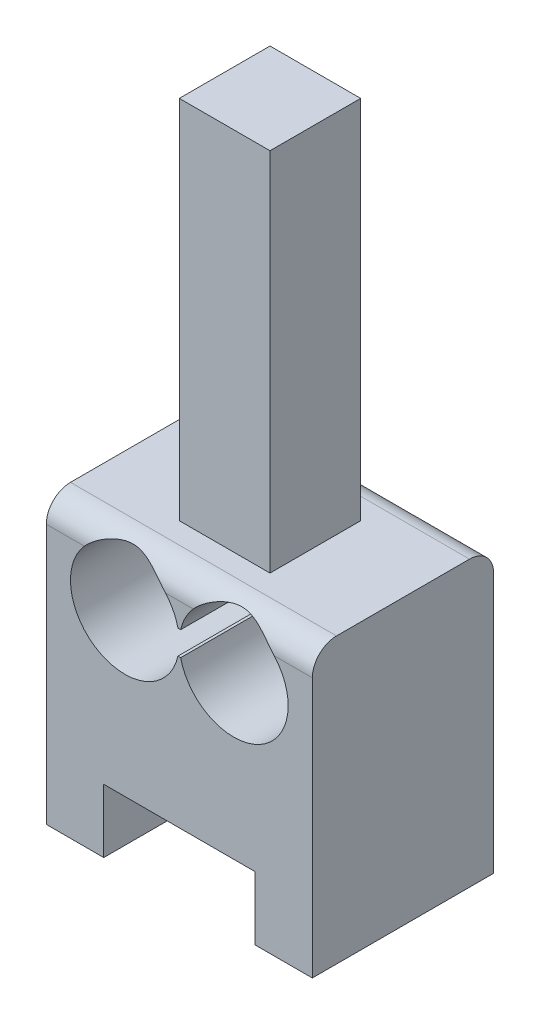
SolidWorks part; units mm, degrees
ref_plane "Front Plane" through (0, 0, 0) normal (0, 0, 1) x (1, 0, 0)
ref_plane "Top Plane" through (0, 0, 0) normal (0, 1, 0) x (1, 0, 0)
ref_plane "Right Plane" through (0, 0, 0) normal (1, 0, 0) x (0, 0, -1)
sketch "Sketch1" plane through (0, 0, 0) normal (0, 0, 1) x (1, 0, 0)
  line L6 (48.0544, -51.8775) -> (48.2794, -51.8775)
  line L19 (51.6669, -45.8775) -> (59.1669, -45.8775)
  line L20 (51.6669, -45.8775) -> (44.6669, -45.8775) construction
  line L21 (41.9169, -64.1275) -> (54.4169, -64.1275)
  line L22 (41.9169, -64.1275) -> (41.9169, -69.3775)
  line L24 (54.4169, -64.1275) -> (54.4169, -69.3775)
  line L25 (59.1669, -69.3775) -> (37.1669, -69.3775)
  line L28 (37.1669, -45.8775) -> (44.6669, -45.8775)
  line L32 (44.6669, -45.8775) -> (51.6669, -45.8775)
  line L33 (37.1669, -45.8775) -> (37.1669, -69.3775)
  line L34 (59.1669, -45.8775) -> (59.1669, -69.3775)
  line L35 (59.1669, -50.8775) -> (37.1669, -50.8775) construction
  line L36 (48.1669, -50.8775) -> (48.1669, 64.3396) construction
  line L38 (48.0544, -49.8775) -> (48.2794, -49.8775)
  arc A0 (48.2794, -51.8775) -> (48.2794, -49.8775) centre (52.6669, -50.8775) ccw
  arc A1 (48.0544, -49.8775) -> (48.0544, -51.8775) centre (43.6669, -50.8775) ccw
  point P0 (0, 0)
  point P9 (51.5, -66.7525)
  point P11 (41.9169, -66.7525)
  dimension "D7" = 9
  dimension "D3" = 12.5
  dimension "D4" = 5
  dimension "D8" = 7.5
  dimension "D9" = 7.5
  dimension "D10" = 23.5
  dimension "D11" = 5.25
  dimension "D12" = 4.75
  dimension "D13" = 9
  dimension "D5" = 22
extrude "pusher base" add sketch "Sketch1" along normal blind 15 contours L32 L28 L19 A1 A0 L21 L24 L22 region at (48.1669, -58.4331, 0)
sketch "Sketch3" plane through (0, -64.1275, 0) normal (0, -1, 0) x (1, 0, 0)
  line L0 (48.1669, 15) -> (48.1669, 0) construction
  line L1 (41.9169, 15) -> (54.4169, 15) construction
  line L2 (41.9169, 0) -> (54.4169, 0) construction
  circle A0 centre (48.1669, 7.5) radius 1.95
  point P10 (48.1669, 7.5)
  dimension "D1" = 3.9
extrude "screw hole" cut sketch "Sketch3" against normal blind 7.5
ref_plane "Plane1" through (0, 0, 7.5) normal (0, 0, 1) x (1, 0, 0)
sketch "Sketch6" plane through (0, 0, 7.5) normal (0, 0, 1) x (1, 0, 0)
  line L0 (41.9169, -64.1275) -> (54.4169, -64.1275) construction
  line L5 (37.1669, -45.8775) -> (59.1669, -45.8775) construction
  line L6 (44.4169, -25.6275) -> (51.9169, -25.6275)
  line L11 (44.4169, -25.6275) -> (44.4169, -45.8775)
  line L12 (44.4169, -45.8775) -> (51.9169, -45.8775)
  line L13 (51.9169, -25.6275) -> (51.9169, -45.8775)
  line L14 (48.1669, -64.1275) -> (48.1669, -27.6275) construction
  line L15 (51.9169, -25.6275) -> (44.4169, -25.6275)
  line L16 (51.9169, -25.6275) -> (51.9169, -15.6275)
  line L17 (51.9169, -15.6275) -> (44.4169, -15.6275)
  line L18 (44.4169, -25.6275) -> (44.4169, -15.6275)
  point P2 (48.1669, -25.6275)
  point P8 (48.1669, -45.8775)
  dimension "D1" = 7.5
  dimension "D3" = 7.5
  dimension "D4" = 10
  dimension "D5" = 38.5
extrude "pusher head" add sketch "Sketch6" along normal mid plane 7.5 contours L18 L15 L6 L16 L17 | L13 L6 L12 | L11 L12 L6 region at (48.1669, -20.6275, 7.5) region at (48.1669, -35.7525, 7.5)
fillet "Fillet1" radius 2 2 edges at (48.1669, -45.8775, 0) (48.1669, -45.8775, 15)
sketch "Sketch12" plane through (44.4169, 0, 0) normal (-1, 0, 0) x (0, 0, 1)
  line L0 (7.5, -15.6275) -> (7.5, -45.8775) construction
  line L1 (11.25, -15.6275) -> (3.75, -15.6275) construction
  line L2 (11.25, -45.8775) -> (3.75, -45.8775) construction
  line L3 (3.75, -30.7525) -> (11.25, -30.7525) construction
  line L4 (3.75, -45.8775) -> (3.75, -15.6275) construction
  line L5 (11.25, -45.8775) -> (11.25, -15.6275) construction
  line L6 (5.8585, -32.7525) -> (3.75, -32.7525)
  line L7 (5.8585, -28.7525) -> (9.1415, -28.7525)
  line L8 (9.1415, -32.7525) -> (11.25, -32.7525)
  line L9 (3.75, -32.7025) -> (5.8585, -32.7025)
  line L10 (11.25, -32.7025) -> (9.1415, -32.7025)
  arc A0 (5.8585, -32.7525) -> (5.8585, -30.7525) centre (5.8585, -31.7525) ccw
  arc A1 (5.8585, -28.7525) -> (5.8585, -30.7525) centre (5.8585, -29.7525) ccw
  arc A2 (9.1415, -32.7525) -> (9.1415, -30.7525) centre (9.1415, -31.7525) cw
  arc A3 (9.1415, -28.7525) -> (9.1415, -30.7525) centre (9.1415, -29.7525) cw
  arc A4 (5.8585, -30.7525) -> (5.8585, -32.7025) centre (5.8585, -31.7275) cw
  arc A5 (9.1415, -30.7525) -> (9.1415, -32.7025) centre (9.1415, -31.7275) ccw
  arc A6 (5.8585, -30.7525) -> (5.8585, -28.7525) centre (5.9027, -29.7525) cw
  arc A7 (9.1415, -30.7525) -> (9.1415, -28.7525) centre (9.0973, -29.7525) ccw
  point P25 (7.5, -28.7525)
  dimension "D1" = 2
  dimension "D2" = 0.05
equation "\"PusherHeight\"=2"
equation "\"PusherWidth\"=11"
equation "\"PusherLongWidth\"=5"
equation "\"RodDiameter\"=0.5"
equation "\"HookLength\"=2.01152"
equation "\"HookHeight\"=0.999652"
equation "\"HookInnerLength\"=2"
equation "\"RodHeightDistance\"=0.4276"
equation "\"RodWidthDistance\"=0.75"
equation "\"PusherDepth\"=2"
equation "\"BuckleShaftDiameter\"=0.383646"
equation "\"BeltBuckleDistance\"=1.5"
equation "\"DowelDiameter\"=0.9"
equation "\"D7@Sketch1\"=\"DowelDiameter\""
equation "\"RodSeperationDistance\"=3.98"
equation "\"BuckleNutDiameter\"=0.39"
equation "\"D1@Sketch3\"=\"BuckleNutDiameter\""
equation "\"belt hole width\"=1.4"
equation "\"pusher height\"=3.5175"
equation "\"pusher slot width\"=0.75"
equation "\"D1@Sketch6\"=\"pusher slot width\""
equation "\"pushing bar width\"=1"
equation "\"D4@Sketch6\"=\"pushing bar width\""
equation "\"doweltotop\"=0.5"
equation "\"D4@Sketch1\"=\"doweltotop\""
equation "\"dowel separation\"=0.9"
equation "\"D13@Sketch1\"=\"dowel separation\""
